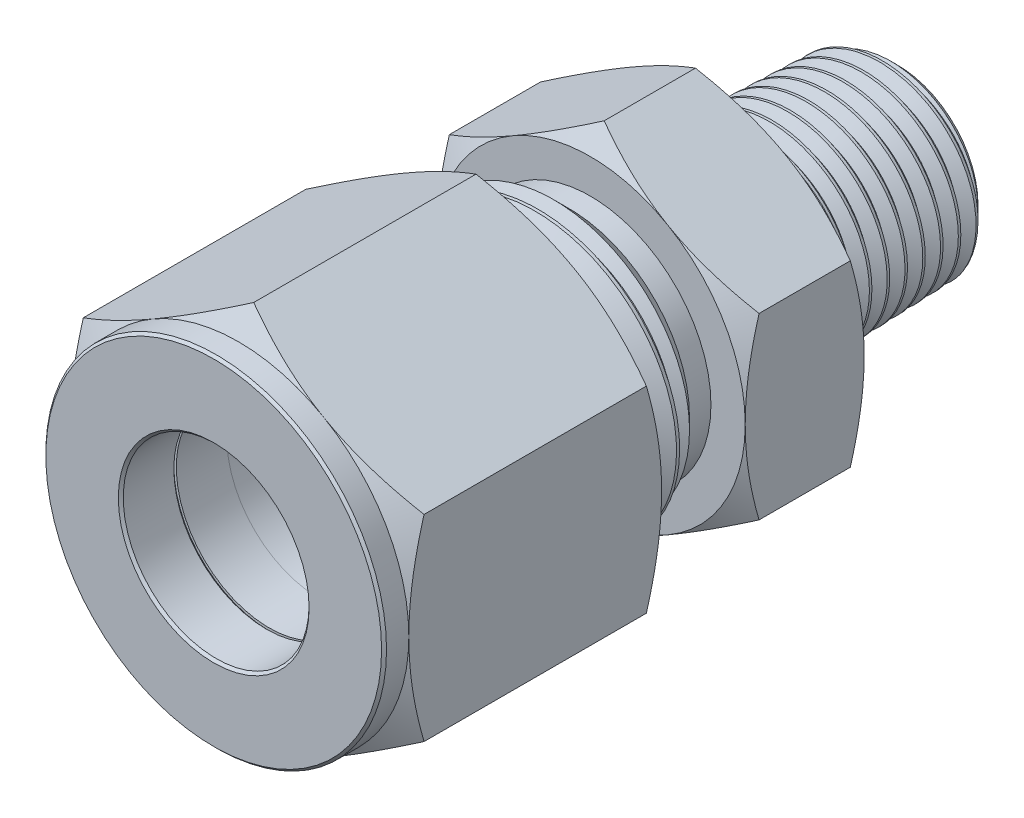
SolidWorks part; units mm, degrees
material "Brass"
ref_plane "Front Plane" through (0, 0, 0) normal (0, 0, 1) x (1, 0, 0)
ref_plane "Top Plane" through (0, 0, 0) normal (0, 1, 0) x (1, 0, 0)
ref_plane "Right Plane" through (0, 0, 0) normal (1, 0, 0) x (0, 0, -1)
sketch "Sketch1" plane through (0, 0, 0) normal (1, 0, 0) x (0, 0, -1)
  line L0 (0, 0) -> (35.052, 0) construction
  line L1 (0, 4.7625) -> (0, -4.7625) construction
  line L2 (14.224, 8.7312) -> (14.224, -8.7312) construction
  line L3 (5.6896, 7.1437) -> (5.6896, -7.1437) construction
  line L4 (5.6896, 7.1437) -> (5.6896, 5.8737) construction
  line L5 (25.4, 7.9375) -> (25.4, -7.9375) construction
  line L6 (4.7625, 6.2865) -> (9.6393, 5.08) construction
  line L7 (9.6393, 5.08) -> (9.6393, 4.7625) construction
  line L8 (9.6393, 4.7625) -> (5.4356, 4.7625) construction
  line L9 (5.4356, 4.7625) -> (4.7625, 5.4356) construction
  line L10 (4.7625, 5.4356) -> (4.7625, 6.2865) construction
  line L11 (2.8448, 6.223) -> (3.9878, 6.223) construction
  line L12 (3.9878, 6.223) -> (3.9878, 5.4356) construction
  line L13 (3.9878, 5.4356) -> (4.7625, 5.4356) construction
  line L14 (25.4, 3.5687) -> (25.4, -3.5687) construction
  line L15 (4.7625, 5.4356) -> (4.7625, 4.7625) construction
  line L16 (5.4356, 4.7625) -> (2.8448, 4.7625) construction
  line L17 (2.8448, 4.7625) -> (2.8448, 6.223) construction
  line L18 (4.7625, 4.7625) -> (5.4356, 4.7625) construction
  line L19 (0, 4.7625) -> (2.8448, 4.7625) construction
  line L20 (2.8448, 4.7625) -> (5.6896, 4.7625) construction
  line L21 (35.052, 4.8332) -> (35.052, -4.8332) construction
  line L22 (25.085, 5.1435) -> (25.085, -5.1435) construction
  line L23 (25.085, 5.1435) -> (35.052, 4.8332) construction
  line L24 (25.085, 5.1435) -> (25.085, 4.2028) construction
  line L25 (28.3489, 5.0419) -> (28.3489, -5.0419) construction
  line L26 (35.052, 3.5687) -> (35.052, -3.5687) construction
  point P4 (1.27, 0)
  point P10 (5.6896, 0)
  point P12 (14.224, 0)
  point P15 (19.304, 0)
  point P16 (7.366, 0)
  point P17 (17.018, 0)
  point P33 (25.4, 0)
  point P40 (25.085, 0)
  point P44 (28.3489, 0)
  dimension "BF OD 2" = 12.446
  dimension "BF Lg" = 2.5908
  dimension "BF Lg 1" = 1.143
  dimension "FF Lg" = 4.8768
  dimension "FF OD 1" = 10.16
  dimension "FF OD 2" = 12.573
  dimension "BF OD 1" = 10.8712
  dimension "Nut Lg" = 14.224
  dimension "Tube OD" = 9.525
  dimension "Nut Hex" = 17.4625
  dimension "Straight Thread OD" = 14.2875
  dimension "Nut Thread Lg" = 8.5344
  dimension "Straight Thread Pitch" = 1.27
  dimension "Lg 1" = 1.27
  dimension "Lg" = 35.052
  dimension "Body Hex" = 15.875
  dimension "C" = 19.304
  dimension "D" = 27.686
  dimension "Insertion Depth" = 17.018
  dimension "E" = 7.1374
  dimension "R" = 9.652
  dimension "Pipe OD" = 10.287
  dimension "A1" = 1.783
  dimension "L4" = 9.967
  dimension "Pipe Pitch" = 0.9407
  dimension "L2" = 6.7031
  dimension "Pipe ID" = 7.1374
sketch "Sketch2" plane through (0, 0, 0) normal (0, 0, 1) x (1, 0, 0)
  line L0 (0, 4.7625) -> (0, -4.7625) construction
  line L1 (0, 10.082) -> (-8.7312, 5.041)
  line L2 (-8.7312, 5.041) -> (-8.7312, -5.041)
  line L3 (-8.7312, -5.041) -> (0, -10.082)
  line L4 (0, -10.082) -> (8.7312, -5.041)
  line L5 (8.7312, -5.041) -> (8.7313, 5.041)
  line L6 (8.7313, 5.041) -> (0, 10.082)
  line L7 (0, 10.082) -> (0, 0) construction
  circle A0 centre (0, 0) radius 8.7312 construction
extrude "Boss-Extrude1" add sketch "Sketch2" against normal up to vertex (14.224 mm away) up to point (0, 0, -14.224)
sketch "Sketch3" plane through (0, 0, 0) normal (1, 0, 0) x (0, 0, -1)
  line L0 (0, 10.082) -> (0, 8.7312)
  line L1 (0, 5.041) -> (0, 10.082) construction
  line L2 (0, 8.7312) -> (1.27, 8.7312)
  line L3 (1.27, 8.7312) -> (2.0498, 10.082)
  line L4 (14.224, 10.082) -> (0, 10.082) construction
  line L5 (2.0498, 10.082) -> (13.4442, 10.082)
  line L6 (13.4442, 10.082) -> (14.224, 8.7312)
  line L7 (14.224, 8.7312) -> (14.224, 10.082)
  line L8 (14.224, 10.082) -> (14.224, 11.4327)
  line L9 (14.224, 11.4327) -> (0, 11.4327)
  line L10 (0, 11.4327) -> (0, 10.082)
  line L11 (0, 4.7625) -> (0, 0)
  line L12 (0, 4.7625) -> (0, -4.7625) construction
  line L13 (0, 0) -> (14.224, 0)
  line L14 (14.224, 8.7312) -> (14.224, -8.7312) construction
  line L15 (14.224, 0) -> (14.224, 7.1438)
  line L16 (14.224, 7.1438) -> (5.6896, 7.1437)
  line L17 (5.6896, 7.1437) -> (5.6896, 5.8737) construction
  line L18 (5.6896, 5.8737) -> (2.8448, 5.8737) construction
  line L19 (2.8448, 5.8737) -> (2.8448, 4.7625)
  line L20 (2.8448, 4.7625) -> (0, 4.7625)
  line L21 (2.8448, 5.8737) -> (2.8448, 7.1437) construction
  line L22 (2.8448, 7.1437) -> (5.6896, 7.1437) construction
  line L23 (5.6896, 6.5087) -> (2.8448, 6.5087)
  line L24 (2.8448, 6.5087) -> (2.8448, 5.8737)
  line L25 (5.6896, 6.5087) -> (5.6896, 7.1437)
  dimension "D1" = 30
  dimension "D2" = 1.27
revolve "Cut-Revolve1" cut sketch "Sketch3" angle 360 about L0
chamfer "Chamfer1" distance 0.127 angle 45 3 edges at (4.7625, 0, 0) (4.7625, 0, -2.8448) (8.7312, 0, 0)
sketch "Sketch4" plane through (0, 0, 0) normal (1, 0, 0) x (0, 0, -1)
  line L1 (25.4, 0) -> (7.366, 0)
  line L2 (25.4, 0) -> (25.4, 7.1438)
  line L3 (25.4, 7.1438) -> (7.366, 7.1437)
  line L4 (7.366, 0) -> (7.366, 7.1437)
  dimension "D1" = 18.034
revolve "Revolve1" add sketch "Sketch4" angle 360 about L1
sketch "Sketch5" plane through (0, 0, -7.366) normal (0, 0, -1) x (-1, 0, 0)
  circle A0 centre (0, 0) radius 7.1438 construction
  circle A1 centre (0, 0) radius 7.1438
  point P3 (0, 7.1438)
curve "Helix/Spiral1" pitch 1.27 height 19.304 turns 15.2
sketch "Sketch6" plane through (0, 0, 0) normal (1, 0, 0) x (0, 0, -1)
  line L0 (6.1754, 7.2812) -> (7.4454, 7.2812) construction
  line L1 (7.4454, 7.2812) -> (6.8104, 6.1814) construction
  line L2 (6.8104, 6.1814) -> (6.1754, 7.2812) construction
  line L3 (6.731, 6.3189) -> (6.8898, 6.3189) construction
  line L4 (6.2547, 7.1438) -> (7.366, 7.1438) construction
  line L5 (6.8104, 6.1814) -> (6.8104, 6.3189) construction
  line L6 (6.8104, 7.1438) -> (6.8104, 7.2812) construction
  line L7 (6.731, 6.3189) -> (6.2151, 7.2125)
  line L8 (6.2151, 7.2125) -> (7.4057, 7.2125)
  line L9 (7.4057, 7.2125) -> (6.8898, 6.3189)
  line L10 (6.8898, 6.3189) -> (6.731, 6.3189)
  point P10 (6.8104, 7.2125)
  dimension "D1" = 1.27
  dimension "D2" = 0.1588
sweep "Cut-Sweep1" cut profiles "Sketch6" path "Helix/Spiral1"
sketch "Sketch7" plane through (0, 0, -25.4) normal (0, 0, -1) x (-1, 0, 0)
  line L0 (0, 0) -> (0, 9.1654) construction
  line L1 (0, 9.1654) -> (-7.9375, 4.5827)
  line L2 (-7.9375, 4.5827) -> (-7.9375, -4.5827)
  line L3 (-7.9375, -4.5827) -> (0, -9.1654)
  line L4 (0, -9.1654) -> (7.9375, -4.5827)
  line L5 (7.9375, -4.5827) -> (7.9375, 4.5827)
  line L6 (7.9375, 4.5827) -> (0, 9.1654)
  circle A0 centre (0, 0) radius 7.9375 construction
extrude "Boss-Extrude2" add sketch "Sketch7" against normal up to vertex (6.096 mm away) up to point (0, 0, -19.304)
sketch "Sketch8" plane through (0, 0, 0) normal (1, 0, 0) x (0, 0, -1)
  line L0 (7.366, 7.2812) -> (7.366, 6.1814)
  line L1 (7.366, 6.1814) -> (8.4659, 7.2812)
  line L2 (8.4659, 7.2812) -> (7.366, 7.2812)
  line L3 (19.304, 7.2812) -> (17.1043, 7.2812)
  line L4 (17.1043, 7.2812) -> (18.2041, 6.1814)
  line L5 (18.2041, 6.1814) -> (19.304, 6.1814)
  line L6 (19.304, 6.1814) -> (19.304, 7.2812)
  line L7 (19.304, 7.9375) -> (20.0129, 9.1654)
  line L8 (19.304, 9.1654) -> (19.304, 4.5827) construction
  line L9 (19.304, 9.1654) -> (25.4, 9.1654) construction
  line L10 (20.0129, 9.1654) -> (24.6911, 9.1654)
  line L11 (17.018, 3.5687) -> (25.4, 3.5687)
  line L12 (24.6911, 9.1654) -> (25.4, 7.9375)
  line L13 (25.4, -4.5827) -> (25.4, 4.5827) construction
  line L14 (25.4, 9.1654) -> (25.4, 10.3934)
  line L15 (25.4, 10.3934) -> (19.304, 10.3934)
  line L16 (19.304, 10.3934) -> (19.304, 9.1654)
  line L17 (19.304, 9.1654) -> (19.304, 7.9375)
  line L18 (6.8104, 6.1814) -> (7.366, 6.1814) construction
  line L19 (7.4454, 7.2812) -> (7.366, 7.2812) construction
  line L20 (8.4659, 7.2812) -> (17.1043, 7.2812) construction
  line L21 (18.2041, 6.1814) -> (7.366, 6.1814) construction
  line L22 (7.366, 5.6424) -> (10.9227, 4.7625)
  line L23 (25.4, 7.9375) -> (25.4, 9.1654)
  line L24 (7.366, 5.0514) -> (7.366, -6.3277) construction
  line L25 (4.7625, 6.2865) -> (9.6393, 5.08) construction
  line L26 (25.4, 0) -> (7.366, 0)
  line L27 (7.366, 0) -> (7.366, 5.6424)
  line L28 (10.9227, 4.7625) -> (17.018, 4.7625)
  line L29 (17.018, 4.7625) -> (17.018, 3.5687)
  line L30 (25.4, 3.5687) -> (25.4, 0)
  line L31 (17.018, 0) -> (17.018, 3.5687) construction
  line L32 (25.4, 7.9375) -> (25.4, -7.9375) construction
  dimension "D1" = 30
revolve "Cut-Revolve2" cut sketch "Sketch8" angle 360 about L0
sketch "Sketch9" plane through (0, 0, 0) normal (1, 0, 0) x (0, 0, -1)
  line L0 (4.7625, 6.2865) -> (4.7625, 5.4356)
  line L1 (4.7625, 5.4356) -> (5.4356, 4.7625)
  line L2 (5.4356, 4.7625) -> (9.6393, 4.7625)
  line L3 (9.6393, 4.7625) -> (9.6393, 5.08)
  line L4 (9.6393, 5.08) -> (4.7625, 6.2865)
revolve "Revolve2" add sketch "Sketch9" angle 360 about L0
sketch "Sketch10" plane through (0, 0, 0) normal (1, 0, 0) x (0, 0, -1)
  line L0 (2.8448, 6.223) -> (3.9878, 6.223)
  line L1 (3.9878, 6.223) -> (3.9878, 5.4356)
  line L2 (3.9878, 5.4356) -> (4.7625, 5.4356)
  line L4 (4.7625, 5.4356) -> (5.4356, 4.7625)
  line L5 (5.4356, 4.7625) -> (2.8448, 4.7625)
  line L6 (2.8448, 4.7625) -> (2.8448, 6.223)
revolve "Revolve3" add sketch "Sketch10" angle 360 about L0
sketch "Sketch11" plane through (0, 0, 0) normal (1, 0, 0) x (0, 0, -1)
  line L0 (25.085, 0) -> (35.052, 0)
  line L1 (35.052, 0) -> (35.052, 4.8332)
  line L2 (35.052, 4.8332) -> (25.085, 5.1435)
  line L3 (25.085, 5.1435) -> (25.085, 0)
revolve "Revolve4" add sketch "Sketch11" angle 360 about L0
sketch "Sketch12" plane through (0, 0, -35.052) normal (0, 0, -1) x (-1, 0, 0)
  circle A1 centre (0, 0) radius 4.8332
  circle A2 centre (0, 0) radius 4.8332
  point P0 (0, 4.8332)
  dimension "D1" = 0
curve "Helix/Spiral2"
sketch "Sketch13" plane through (0, 0, 0) normal (1, 0, 0) x (0, 0, -1)
  line L0 (34.9932, 4.935) -> (35.9339, 4.935) construction
  line L1 (34.9932, 4.935) -> (35.4636, 4.1203) construction
  line L2 (35.4636, 4.1203) -> (35.9339, 4.935) construction
  line L3 (35.4048, 4.2221) -> (35.5224, 4.2221) construction
  line L4 (35.052, 4.8332) -> (35.8751, 4.8332) construction
  line L5 (35.4636, 4.1203) -> (35.4636, 4.2221) construction
  line L6 (35.4636, 4.8332) -> (35.4636, 4.935) construction
  line L7 (35.4636, 4.8841) -> (35.9045, 4.8841) construction
  line L8 (35.4636, 4.1203) -> (35.4636, -4.8204) construction
  line L9 (35.4636, -4.8204) -> (34.5233, -4.8496) construction
  line L10 (34.5233, -4.8496) -> (33.583, -4.8789) construction
  line L11 (33.583, -4.8789) -> (32.6427, -4.9082) construction
  line L12 (34.9932, 4.935) -> (35.9045, 4.8841)
  line L13 (35.9045, 4.8841) -> (35.5224, 4.2221)
  line L14 (35.5224, 4.2221) -> (35.4048, 4.2221)
  line L15 (35.4048, 4.2221) -> (34.9932, 4.935)
  line L16 (25.085, -5.1435) -> (35.052, -4.8332) construction
  line L17 (32.6427, -4.9082) -> (31.7024, -4.9375) construction
  line L18 (31.7024, -4.9375) -> (30.7621, -4.9667) construction
  dimension "D1" = 0.9407
  dimension "D2" = 0.1176
sweep "Cut-Sweep2" cut profiles "Sketch13" path "Helix/Spiral2"
combine bodies "Combine1" operation type add bodies to combine 113 122
sketch "Sketch14" plane through (0, 0, 0) normal (1, 0, 0) x (0, 0, -1)
  line L0 (35.4636, 4.1203) -> (35.052, 4.1203) construction
  line L5 (35.052, 4.8332) -> (35.052, -4.8332) construction
  line L6 (35.052, 4.1203) -> (34.2373, 4.935)
  line L7 (34.2373, 4.935) -> (35.052, 4.935)
  line L8 (35.052, 4.935) -> (35.052, 4.1203)
  line L9 (34.9932, 4.935) -> (35.9339, 4.935) construction
  line L10 (35.052, 3.5687) -> (25.085, 3.5687)
  line L11 (25.085, 3.5687) -> (25.085, 0) construction
  line L12 (22.9407, 0) -> (35.052, 0)
  line L13 (22.9407, 0) -> (25.085, 3.5687)
  line L14 (35.052, 0) -> (35.052, 3.5687)
  dimension "D1" = 59
revolve "Cut-Revolve4" cut sketch "Sketch14" angle 360 about L0
equation "\"D4@Helix/Spiral1\" = \"Straight Thread Pitch@Sketch1\""
equation "\"D3@Helix/Spiral1\" = \"D4@Helix/Spiral1\" + \"D1@Sketch4\""
equation "\"D1@Sketch6\" = \"D4@Helix/Spiral1\""
equation "\"D2@Sketch6\" = \"D1@Sketch6\" / 8"
equation "\"D4@Helix/Spiral2\" = \"Pipe Pitch@Sketch1\""
equation "\"D3@Helix/Spiral2\" = \"D4@Helix/Spiral2\" + \"L4@Sketch1\""
equation "\"D1@Sketch13\" = \"D4@Helix/Spiral2\""
equation "\"D2@Sketch13\" = \"D1@Sketch13\" / 8"
